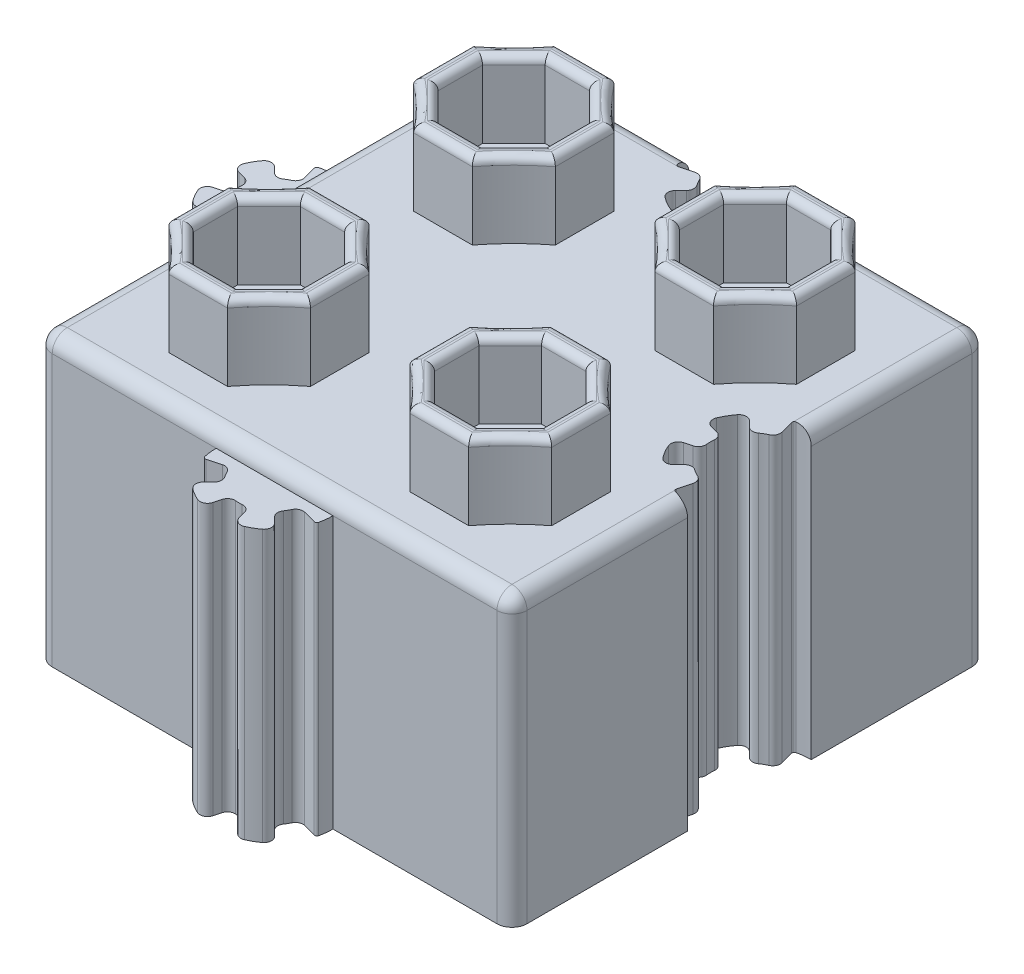
SolidWorks part; units mm, degrees
ref_plane "Front Plane" through (0, 0, 0) normal (0, 0, 1) x (1, 0, 0)
ref_plane "Top Plane" through (0, 0, 0) normal (0, 1, 0) x (1, 0, 0)
ref_plane "Right Plane" through (0, 0, 0) normal (1, 0, 0) x (0, 0, -1)
sketch "Sketch2" plane through (0, 0, 0) normal (0, 1, 0) x (1, 0, 0)
  line L1 (-15.75, 15.75) -> (15.75, 15.75)
  line L2 (-15.75, 15.75) -> (-15.75, -15.75)
  line L3 (-15.75, -15.75) -> (15.75, -15.75)
  line L4 (15.75, 15.75) -> (15.75, -15.75)
  line L5 (-15.75, 15.75) -> (15.75, -15.75) construction
  line L6 (-15.75, -15.75) -> (15.75, 15.75) construction
  point P0 (0, 0)
  dimension "D1" = 31.5
  dimension "D2" = 31.5
extrude "Boss-Extrude1" add sketch "Sketch2" along normal blind 19
sketch "Sketch3" plane through (0, 19, 0) normal (0, 1, 0) x (1, 0, 0)
  line L97 (-15.75, 15.75) -> (-8, 15.75)
  line L98 (15.75, 15.75) -> (-15.75, 15.75) construction
  line L101 (-15.75, 15.75) -> (-15.75, 8)
  line L102 (-15.75, 15.75) -> (-15.75, -15.75) construction
  line L103 (-3.3, 6.1743) -> (-3.3, 10.0679)
  line L105 (-6.0532, 12.8211) -> (-9.9468, 12.8211)
  line L107 (-12.7, 10.0679) -> (-12.7, 6.1743)
  line L109 (-9.9468, 3.4211) -> (-6.0532, 3.4211)
  line L110 (-6.5295, 4.5711) -> (-4.45, 6.6506)
  line L111 (-4.45, 6.6506) -> (-4.45, 9.5916)
  line L112 (-4.45, 9.5916) -> (-6.5295, 11.6711)
  line L113 (-6.5295, 11.6711) -> (-9.4705, 11.6711)
  line L114 (-9.4705, 11.6711) -> (-11.55, 9.5916)
  line L115 (-11.55, 9.5916) -> (-11.55, 6.6506)
  line L116 (-11.55, 6.6506) -> (-9.4705, 4.5711)
  line L117 (-9.4705, 4.5711) -> (-6.5295, 4.5711)
  line L118 (-9.9468, 12.8211) -> (-12.7, 10.0679) [skipped]
  line L119 (-3.3, 10.0679) -> (-6.0532, 12.8211) [skipped]
  line L120 (-6.0532, 3.4211) -> (-3.3, 6.1743) [skipped]
  line L121 (-12.7, 6.1743) -> (-9.9468, 3.4211) [skipped]
  line L125 (9.4705, 4.5711) -> (6.5295, 4.5711)
  line L126 (11.55, 6.6506) -> (9.4705, 4.5711)
  line L127 (11.55, 9.5916) -> (11.55, 6.6506)
  line L128 (9.4705, 11.6711) -> (11.55, 9.5916)
  line L129 (6.5295, 11.6711) -> (9.4705, 11.6711)
  line L130 (4.45, 9.5916) -> (6.5295, 11.6711)
  line L131 (4.45, 6.6506) -> (4.45, 9.5916)
  line L132 (6.5295, 4.5711) -> (4.45, 6.6506)
  line L133 (9.9468, 3.4211) -> (6.0532, 3.4211)
  line L134 (12.7, 10.0679) -> (12.7, 6.1743)
  line L135 (6.0532, 12.8211) -> (9.9468, 12.8211)
  line L136 (3.3, 6.1743) -> (3.3, 10.0679)
  line L137 (3.3, -6.1743) -> (3.3, -10.0679)
  line L138 (6.0532, -12.8211) -> (9.9468, -12.8211)
  line L139 (12.7, -10.0679) -> (12.7, -6.1743)
  line L140 (9.9468, -3.4211) -> (6.0532, -3.4211)
  line L141 (6.5295, -4.5711) -> (4.45, -6.6506)
  line L142 (4.45, -6.6506) -> (4.45, -9.5916)
  line L143 (4.45, -9.5916) -> (6.5295, -11.6711)
  line L144 (6.5295, -11.6711) -> (9.4705, -11.6711)
  line L145 (9.4705, -11.6711) -> (11.55, -9.5916)
  line L146 (11.55, -9.5916) -> (11.55, -6.6506)
  line L147 (11.55, -6.6506) -> (9.4705, -4.5711)
  line L148 (9.4705, -4.5711) -> (6.5295, -4.5711)
  line L149 (-9.4705, -4.5711) -> (-6.5295, -4.5711)
  line L150 (-11.55, -6.6506) -> (-9.4705, -4.5711)
  line L151 (-11.55, -9.5916) -> (-11.55, -6.6506)
  line L152 (-9.4705, -11.6711) -> (-11.55, -9.5916)
  line L153 (-6.5295, -11.6711) -> (-9.4705, -11.6711)
  line L154 (-4.45, -9.5916) -> (-6.5295, -11.6711)
  line L155 (-4.45, -6.6506) -> (-4.45, -9.5916)
  line L156 (-6.5295, -4.5711) -> (-4.45, -6.6506)
  line L157 (-9.9468, -3.4211) -> (-6.0532, -3.4211)
  line L158 (-12.7, -10.0679) -> (-12.7, -6.1743)
  line L159 (-6.0532, -12.8211) -> (-9.9468, -12.8211)
  line L160 (-3.3, -6.1743) -> (-3.3, -10.0679)
  arc A2 (-12.7, 10.0679) -> (-9.9468, 12.8211) centre (-21.8403, 21.9614) ccw
  arc A3 (-6.0532, 12.8211) -> (-3.3, 10.0679) centre (5.8403, 21.9614) ccw
  arc A4 (-6.0532, 3.4211) -> (-3.3, 6.1743) centre (5.8403, -5.7192) cw
  arc A5 (-9.9468, 3.4211) -> (-12.7, 6.1743) centre (-21.8403, -5.7192) ccw
  arc A6 (9.9468, 3.4211) -> (12.7, 6.1743) centre (21.8403, -5.7192) cw
  arc A7 (6.0532, 3.4211) -> (3.3, 6.1743) centre (-5.8403, -5.7192) ccw
  arc A8 (6.0532, 12.8211) -> (3.3, 10.0679) centre (-5.8403, 21.9614) cw
  arc A9 (12.7, 10.0679) -> (9.9468, 12.8211) centre (21.8403, 21.9614) cw
  arc A10 (12.7, -10.0679) -> (9.9468, -12.8211) centre (21.8403, -21.9614) ccw
  arc A11 (6.0532, -12.8211) -> (3.3, -10.0679) centre (-5.8403, -21.9614) ccw
  arc A12 (6.0532, -3.4211) -> (3.3, -6.1743) centre (-5.8403, 5.7192) cw
  arc A13 (9.9468, -3.4211) -> (12.7, -6.1743) centre (21.8403, 5.7192) ccw
  arc A14 (-9.9468, -3.4211) -> (-12.7, -6.1743) centre (-21.8403, 5.7192) cw
  arc A15 (-6.0532, -3.4211) -> (-3.3, -6.1743) centre (5.8403, 5.7192) ccw
  arc A16 (-6.0532, -12.8211) -> (-3.3, -10.0679) centre (5.8403, -21.9614) cw
  arc A17 (-12.7, -10.0679) -> (-9.9468, -12.8211) centre (-21.8403, -21.9614) cw
  point P4 (-8, 8.1211)
  point P52 (8, 8.1211)
  point P95 (8, -8.1211)
  point P96 (-8, -8.1211)
  dimension "D3" = 15
  dimension "D4" = 15
  dimension "D5" = 15
  dimension "D6" = 15
  dimension "D1" = 7.75
  dimension "D2" = 7.75
sketch "Sketch5" plane through (0, 19, 0) normal (0, 1, 0) x (1, 0, 0)
  line L0 (15.75, 15.75) -> (-15.75, 15.75) construction
  line L1 (0.647, 13.3352) -> (1.0353, 11.8863)
  line L2 (-4, 15.75) -> (4, 15.75)
  line L3 (-2.4148, 15.103) -> (-3.8637, 14.7147)
  line L4 (-1.7678, 13.9822) -> (-2.8284, 12.9216)
  line L5 (2.4148, 15.103) -> (3.8637, 14.7147)
  line L6 (-0.647, 13.3352) -> (-1.0353, 11.8863)
  line L7 (1.7678, 13.9822) -> (2.8284, 12.9216)
  line L8 (0, 15.75) -> (4, 15.75)
  line L10 (15.75, 2.6) -> (15.75, -2.6)
  line L12 (15.75, -15.75) -> (15.75, 15.75) construction
  line L16 (13.2386, 0.6729) -> (11.7897, 1.0612)
  line L18 (13.9115, 1.8385) -> (12.8509, 2.8991)
  line L20 (15.0771, 2.5114) -> (14.6888, 3.9603)
  line L21 (15.75, 2.6) -> (15.75, 4.1)
  line L33 (15.75, -2.6) -> (15.75, -4.1)
  line L34 (15.0771, -2.5114) -> (14.6888, -3.9603)
  line L36 (13.9115, -1.8385) -> (12.8509, -2.8991)
  line L38 (13.2386, -0.6729) -> (11.7897, -1.0612)
  arc A0 (-4, 15.75) -> (4, 15.75) centre (0, 15.75) ccw
  arc A1 (-2.4148, 15.103) -> (-1.7678, 13.9822) centre (0, 15.75) ccw
  arc A4 (15.75, 4.1) -> (15.75, -4.1) centre (15.75, 0) ccw
  arc A5 (15.0771, 2.5114) -> (13.9115, 1.8385) centre (15.75, 0) ccw
  arc A6 (13.2386, 0.6729) -> (13.2386, -0.6729) centre (15.75, 0) ccw
  arc A7 (13.9115, -1.8385) -> (15.0771, -2.5114) centre (15.75, 0) ccw
  arc A8 (1.7678, 13.9822) -> (2.4148, 15.103) centre (0, 15.75) ccw
  arc A9 (-0.647, 13.3352) -> (0.647, 13.3352) centre (0, 15.75) ccw
  point P52 (15.75, 0)
  line M12 (15.75, -15.75) -> (15.75, 15.75)
  line M13 (15.75, 15.75) -> (-15.75, 15.75)
  dimension "D1" = 5
  dimension "D4" = 5.2
  dimension "D2" = 4
  dimension "D3" = 8.2
extrude "Cut-Extrude6" cut sketch "Sketch5" against normal through all contours L6 A9 L1 A0 L7 A8 L5 L2 L3 A1 L4 M13 | L36 A7 L34 A4 L20 A5 L18 L16 A6 L38 M12 region at (0, 19, -14.2637) region at (14.2251, 19, 0)
sketch "Sketch6" plane through (0, 19, 0) normal (0, 1, 0) x (1, 0, 0)
  line L0 (-15.75, -15.75) -> (15.75, -15.75) construction
  line L2 (-2.2941, -16.3647) -> (-3.743, -16.7529)
  line L9 (-1.6794, -17.4294) -> (-2.74, -18.49)
  line L10 (-0.6201, -18.0426) -> (-1.0118, -19.4906)
  line L11 (0.6201, -18.0426) -> (1.0118, -19.4906)
  line L12 (1.6794, -17.4294) -> (2.74, -18.49)
  line L13 (2.2941, -16.3647) -> (3.743, -16.7529)
  line L14 (-1, -15.75) -> (1, -15.75)
  line L15 (-2.375, -15.75) -> (2.375, -15.75)
  line L16 (-15.75, 0) -> (-15.75, 2.375)
  line L17 (-15.75, 15.75) -> (-15.75, -15.75) construction
  line L18 (-15.75, 2.375) -> (-15.75, -2.375)
  line L19 (-15.75, 3.875) -> (-15.75, -3.875)
  line L20 (-3.875, -15.75) -> (3.875, -15.75)
  line L21 (-16.3647, 2.2941) -> (-16.7529, 3.743)
  line L22 (-16.3647, -2.2941) -> (-16.7529, -3.743)
  line L23 (-17.4294, 1.6794) -> (-18.49, 2.74)
  line L24 (-18.0441, 0.6147) -> (-19.493, 1.0029)
  line L25 (-17.4294, -1.6794) -> (-18.49, -2.74)
  line L26 (-18.0441, -0.6147) -> (-19.493, -1.0029)
  line L27 (-15.75, 2.375) -> (-15.75, -2.375)
  arc A4 (-3.743, -16.7529) -> (-2.74, -18.49) centre (0, -15.75) ccw
  arc A5 (-1.0118, -19.4906) -> (1.0118, -19.4906) centre (0, -15.75) ccw
  arc A6 (2.74, -18.49) -> (3.743, -16.7529) centre (0, -15.75) ccw
  arc A13 (-0.6201, -18.0426) -> (-0.6147, -18.0441) centre (0, -15.75) ccw
  arc A21 (-16.7529, 3.743) -> (-18.49, 2.74) centre (-15.75, 0) ccw
  arc A23 (-19.493, 1.0029) -> (-19.493, -1.0029) centre (-15.75, 0) ccw
  arc A24 (-18.49, -2.74) -> (-16.7529, -3.743) centre (-15.75, 0) ccw
  arc A25 (-16.3647, 2.2941) -> (-17.4294, 1.6794) centre (-15.75, 0) ccw
  arc A27 (-18.0441, 0.6147) -> (-18.0441, -0.6147) centre (-15.75, 0) ccw
  arc A28 (-15.75, 3.875) -> (-15.75, -3.875) centre (-15.75, 0) ccw
  arc A29 (-3.875, -15.75) -> (3.875, -15.75) centre (0, -15.75) ccw
  arc A30 (-2.2941, -16.3647) -> (-1.6794, -17.4294) centre (0, -15.75) ccw
  arc A31 (-17.4294, -1.6794) -> (-16.3647, -2.2941) centre (-15.75, 0) ccw
  arc A32 (1.6794, -17.4294) -> (2.2941, -16.3647) centre (0, -15.75) ccw
  arc A33 (-0.6201, -18.0426) -> (0.6201, -18.0426) centre (0, -15.75) ccw
  line M21 (-15.75, 15.75) -> (-15.75, -15.75)
  line M22 (-15.75, -15.75) -> (15.75, -15.75)
  dimension "D1" = 7.75
  dimension "D2" = 3.875
  dimension "D5" = 4.75
  dimension "D6" = 7.75
  dimension "D4" = 4.75
  dimension "D7" = 7.75
sketch "Sketch7" plane through (0, 0, 0) normal (0, -1, 0) x (1, 0, 0)
  line L4 (0.6, 14.3) -> (7.5717, 14.3)
  line L6 (-14.325, 14.3) -> (-14.325, 7.3)
  line L7 (14.3, 14.3) -> (14.3, 7.3)
  line L16 (14.3, -14.325) -> (7.3, -14.325)
  line L19 (-14.325, -14.3) -> (-7.325, -14.3)
  line L20 (-14.325, 14.3) -> (-7.325, 14.3)
  line L21 (-0.6038, 14.3) -> (-0.6038, 8.175)
  line L22 (-8.2, 0.6) -> (-4.9639, 0.6)
  line L23 (14.3, -4.26) -> (14.3, -6.725)
  line L24 (-14.325, 14.3) -> (-7.325, 14.3)
  line L25 (-14.325, 0.6) -> (-8.2, 0.6)
  line L26 (-14.325, -0.6) -> (-8.2, -0.6)
  line L27 (-14.325, -0.6) -> (-14.325, -6.725)
  line L29 (0.6, 14.3) -> (0.6, 8.175)
  line L30 (1.0353, 3.8637) -> (0.647, 2.4148)
  line L31 (-8.2, -0.6) -> (-4.9639, -0.6)
  line L33 (2.8284, 2.8284) -> (1.7678, 1.7678)
  line L34 (12.65, -7.025) -> (12.65, -6.725)
  line L36 (-14.325, -5.275) -> (-14.325, -6.725)
  line L39 (-7.325, 14.3) -> (-7.325, 12.65)
  line L40 (-7.325, 12.65) -> (-6.725, 12.65)
  line L41 (-6.725, 12.65) -> (-6.725, 14.3)
  line L47 (-7.325, -14.3) -> (-7.325, -12.65)
  line L48 (-7.325, -12.65) -> (-6.725, -12.65)
  line L49 (-6.725, -12.65) -> (-6.725, -14.3)
  line L50 (-14.325, -7.3) -> (-14.325, -14.3)
  line L51 (8.1717, 12.65) -> (7.5717, 12.65)
  line L52 (7.3, -12.525) -> (7.3, -14.325)
  line L53 (7.5717, 12.65) -> (7.5717, 14.3)
  line L54 (-6.725, -14.3) -> (-4.26, -14.3)
  line L55 (-14.325, 7.3) -> (-12.525, 7.3)
  line L56 (-12.675, -6.7) -> (-12.675, -7.3)
  line L57 (-14.325, 6.7) -> (-12.525, 6.7)
  line L58 (8.1717, 12.65) -> (8.1717, 14.3)
  line L59 (6.7, -14.325) -> (4.2684, -14.325)
  line L60 (7.3, -12.525) -> (6.7, -12.525)
  line L61 (6.7, -12.525) -> (6.7, -14.325)
  line L62 (-12.525, 6.7) -> (-12.525, 7.3)
  line L64 (12.5, 7) -> (12.5, 7.3)
  line L65 (12.5, 7.3) -> (14.3, 7.3)
  line L67 (14.3, 6.7) -> (12.5, 6.7)
  line L68 (12.5, 6.7) -> (12.5, 7)
  line L69 (12.65, -6.725) -> (14.3, -6.725)
  line L71 (-12.675, -6.7) -> (-12.675, -6.725)
  line L72 (-12.675, -6.725) -> (-14.325, -6.725)
  line L73 (-12.675, -7.3) -> (-14.325, -7.3)
  line L74 (14.3, -7.325) -> (12.65, -7.325)
  line L75 (12.65, -7.325) -> (12.65, -7.025)
  line L84 (5.0205, 3.9598) -> (4.0279, 2.9624)
  line L90 (3.8637, 1.0353) -> (2.4148, 0.647)
  line L97 (4.4901, 4.4901) -> (5.0205, 3.9598)
  line L98 (3.8637, -1.0353) -> (2.4148, -0.647)
  line L99 (8.2, 0.6) -> (11.2902, 0.6)
  line L100 (8.2, -0.6) -> (11.2902, -0.6)
  line L101 (-0.6038, -8.175) -> (-0.6038, -11.2907)
  line L102 (0.6, -8.175) -> (0.6, -11.2902)
  line L103 (-4.4901, 4.4901) -> (-3.9598, 5.0205)
  line L104 (2.8284, -2.8284) -> (1.7678, -1.7678)
  line L105 (-3.9598, 5.0205) -> (-2.9652, 4.0259)
  line L106 (1.0353, -3.8637) -> (0.647, -2.4148)
  line L107 (-4.4901, 4.4901) -> (-5.0205, 3.9598)
  line L108 (-1.0353, -3.8637) -> (-0.647, -2.4148)
  line L109 (-5.0205, 3.9598) -> (-4.0279, 2.9624)
  line L110 (-2.8284, -2.8284) -> (-1.7678, -1.7678)
  line L111 (3.9598, 5.0205) -> (2.9652, 4.0259)
  line L112 (-3.8637, -1.0353) -> (-2.4148, -0.647)
  line L113 (-6.725, 14.3) -> (-0.6038, 14.3)
  line L114 (8.1717, 14.3) -> (14.3, 14.3)
  line L115 (14.3, 6.7) -> (14.3, 4.26)
  line L116 (-14.325, 6.7) -> (-14.325, 0.6)
  line L117 (7.3, -14.325) -> (14.3, -14.325)
  line L118 (14.3, -7.325) -> (14.3, -14.325)
  line L119 (4.4901, 4.4901) -> (3.9598, 5.0205)
  line L120 (-3.8637, 1.0353) -> (-2.4148, 0.647)
  line L121 (5.0205, -3.9598) -> (4.0279, -2.9624)
  line L122 (-2.8284, 2.8284) -> (-1.7678, 1.7678)
  line L123 (4.4901, -4.4901) -> (5.0205, -3.9598)
  line L124 (-1.0353, 3.8637) -> (-0.647, 2.4148)
  line L130 (4.4901, -4.4901) -> (3.9598, -5.0205)
  line L131 (3.9598, -5.0205) -> (2.9652, -4.0259)
  line L132 (-5.0205, -3.9598) -> (-4.0279, -2.9624)
  line L133 (-4.4901, -4.4901) -> (-5.0205, -3.9598)
  line L134 (-4.4901, -4.4901) -> (-3.9598, -5.0205)
  line L135 (-3.9598, -5.0205) -> (-2.9652, -4.0259)
  line L136 (8.2, 0.6) -> (4.9639, 0.6)
  line L137 (8.2, -0.6) -> (4.9639, -0.6)
  line L138 (-0.6038, 8.175) -> (-0.6038, 4.9634)
  line L139 (0.6, 8.175) -> (0.6, 4.9639)
  line L140 (-0.6038, -8.175) -> (-0.6038, -4.9634)
  line L141 (0.6, -8.175) -> (0.6, -4.9639)
  line L142 (4.2684, -14.325) -> (6.7, -14.325)
  arc A4 (-4.0279, 2.9624) -> (-4.9639, 0.6) centre (0, 0) ccw
  circle A5 centre (0, 0) radius 4
  arc A6 (0.647, 2.4148) -> (-0.647, 2.4148) centre (0, 0) ccw
  arc A7 (2.4148, 0.647) -> (1.7678, 1.7678) centre (0, 0) ccw
  arc A8 (1.7678, -1.7678) -> (2.4148, -0.647) centre (0, 0) ccw
  arc A9 (-0.647, -2.4148) -> (0.647, -2.4148) centre (0, 0) ccw
  arc A10 (-2.4148, -0.647) -> (-1.7678, -1.7678) centre (0, 0) ccw
  arc A11 (-1.7678, 1.7678) -> (-2.4148, 0.647) centre (0, 0) ccw
  arc A12 (2.9652, 4.0259) -> (0.6, 4.9639) centre (0, 0) ccw
  arc A13 (4.0279, -2.9624) -> (4.9639, -0.6) centre (0, 0) ccw
  arc A14 (-2.9652, -4.0259) -> (-0.6038, -4.9634) centre (0, 0) ccw
  arc A15 (-0.6038, 4.9634) -> (-2.9652, 4.0259) centre (0, 0) ccw
  arc A16 (4.9639, 0.6) -> (4.0279, 2.9624) centre (0, 0) ccw
  arc A17 (-4.9639, -0.6) -> (-4.0279, -2.9624) centre (0, 0) ccw
  arc A18 (0.6, -4.9639) -> (2.9652, -4.0259) centre (0, 0) ccw
  arc A19 (14.3, 4.26) -> (14.3, -4.26) centre (15.75, 0) ccw
  arc A20 (4.2684, -14.325) -> (-4.26, -14.3) centre (0, -15.75) ccw
  point P2 (0, 0)
  point P106 (0, 0)
  dimension "D4" = 10
  dimension "D5" = 8
  dimension "D12" = 5
  dimension "D13" = 9
  dimension "D14" = 9
  dimension "D1" = 1.8
  dimension "D2" = 1.65
  dimension "D3" = 1.65
  dimension "D6" = 0.6
  dimension "D7" = 1.8
  dimension "D8" = 1.65
  dimension "D9" = 1.65
  dimension "D10" = 1.8
  dimension "D11" = 1.65
  dimension "D17" = 7
  dimension "D18" = 0.6
  dimension "D19" = 0.6
  dimension "D20" = 0.3
  dimension "D21" = 0.3
  dimension "D22" = 7
  dimension "D23" = 7
  dimension "D24" = 0.6
  dimension "D25" = 0.3
  dimension "D26" = 0.3
  dimension "D27" = 7
  dimension "D28" = 7
  dimension "D29" = 0.6
  dimension "D30" = 7
  dimension "D31" = 7
  dimension "D32" = 0.75
  dimension "D33" = 0.75
fillet "Fillet20" radius 1 10 edges at (15.75, 9.5, 15.75) (15.75, 9.5, -15.75) (-15.75, 9.5, -15.75) (-15.75, 9.5, 15.75) (-9.875, 19, -15.75) (9.875, 19, -15.75) (15.75, 19, 9.925) (15.75, 19, -9.925) (0, 19, 15.75) (-15.75, 19, 0)
extrude "Boss-Extrude7" add sketch "Sketch6" against normal through all from offset 1 contours L21 A21 L23 L24 A23 L26 L25 A24 L22 M21 | L11 L12 A6 L13 L2 A4 L9 A13 L10 A5 M22 region at (0, 19, 17.1861) region at (-17.1883, 19, 0) offset against normal yes
sketch "Sketch16" plane through (0, 0, 0) normal (0, -1, 0) x (1, 0, 0)
  line L0 (-14.3, 14.3) -> (-8.175, 14.3)
  line L4 (-6.725, 12.6) -> (-6.725, 14.3) construction
  line L5 (-6.725, 14.3) -> (-0.6038, 14.3) construction
  line L9 (8.1717, 14.3) -> (14.3, 14.3)
  line L10 (14.3, 14.3) -> (14.3, 8.175)
  line L11 (14.3, 14.3) -> (14.3, 8.175) construction
  line L12 (14.3, 14.3) -> (14.3, 8.175) construction
  line L16 (14.3, 6.725) -> (14.3, 4.6233)
  line L17 (14.3, -4.6233) -> (14.3, -6.725)
  line L18 (14.3, -6.725) -> (12.6, -6.725)
  line L21 (14.3, -8.175) -> (14.3, -14.3)
  line L22 (14.3, -14.3) -> (8.3504, -14.3)
  line L23 (14.3, -14.3) -> (8.1717, -14.3) construction
  line L24 (8.3504, -14.3) -> (8.1717, -14.3)
  line L28 (6.7217, -14.3) -> (4.6233, -14.3)
  line L29 (-4.6233, -14.3) -> (-6.725, -14.3)
  line L31 (-8.175, -14.3) -> (-14.3, -14.3)
  line L32 (-14.3, -14.3) -> (-14.3, -8.175)
  line L35 (-14.3, -6.725) -> (-14.3, 6.725)
  line L38 (-14.3, 8.175) -> (-14.3, 14.3)
  line L42 (-6.725, 14.3) -> (6.7217, 14.3)
  line L44 (14.3, 8.175) -> (12.6, 8.175)
  line L45 (14.3, 6.725) -> (12.6, 6.725)
  line L46 (12.5, 8.075) -> (12.5, 6.825)
  line L47 (8.1717, 14.3) -> (8.1717, 12.6)
  line L48 (6.7217, 14.3) -> (6.7217, 12.6)
  line L49 (6.8217, 12.5) -> (8.0717, 12.5)
  line L50 (-8.175, 14.3) -> (-8.175, 12.6)
  line L51 (-6.725, 14.3) -> (-6.725, 12.6)
  line L52 (-8.075, 12.5) -> (-6.825, 12.5)
  line L53 (-14.3, 8.175) -> (-12.6, 8.175)
  line L54 (-14.3, 6.725) -> (-12.6, 6.725)
  line L55 (-12.5, 8.075) -> (-12.5, 6.825)
  line L56 (14.3, -8.175) -> (12.6, -8.175)
  line L57 (12.5, -6.825) -> (12.5, -8.075)
  line L58 (8.1717, -14.3) -> (8.1717, -12.6)
  line L59 (-6.725, -12.6) -> (-6.725, -14.3)
  line L60 (8.0717, -12.5) -> (6.8217, -12.5)
  line L61 (8.0717, -12.5) -> (6.8217, -12.5) construction
  line L63 (6.7217, -12.6) -> (6.7217, -14.3)
  line L64 (-14.3, -8.175) -> (-12.6, -8.175)
  line L65 (-6.825, -12.5) -> (-8.075, -12.5)
  line L66 (8.175, -0.6) -> (11.3911, -0.6) construction
  line L67 (-8.175, -12.6) -> (-8.175, -14.3)
  line L68 (-12.5, -8.075) -> (-12.5, -6.825)
  line L70 (-12.6, -6.725) -> (-14.3, -6.725)
  line L71 (8.175, 0.6) -> (11.3911, 0.6) construction
  line L73 (4.6233, -14.3) -> (4.5758, -14.3)
  line L75 (6.7217, -14.3) -> (4.1542, -14.3) construction
  line L76 (-4.6233, -14.3) -> (-4.5758, -14.3)
  line L77 (-6.725, -14.3) -> (-4.1542, -14.3) construction
  arc A6 (14.3, 4.6233) -> (10.828, 0.6) centre (15.5903, 0) ccw
  arc A14 (-0.6038, -10.9881) -> (-4.5758, -14.3) centre (0, -15.75) ccw
  arc A15 (10.828, -0.6) -> (14.3, -4.6233) centre (15.5903, 0) ccw
  arc A19 (4.5758, -14.3) -> (0.6005, -10.9877) centre (0, -15.75) ccw
  arc A22 (10.828, 0.6) -> (10.828, -0.6) centre (14.7827, 0) ccw
  arc A24 (-0.6038, -10.9881) -> (0.6005, -10.9877) centre (-0.0003, -14.9423) cw
  arc A31 (-12.5, 8.075) -> (-12.6, 8.175) centre (-12.6, 8.075) ccw construction
  arc A32 (-12.5, 8.075) -> (-12.6, 8.175) centre (-12.6, 8.075) ccw construction
  arc A33 (-12.6, 8.175) -> (-12.5, 8.075) centre (-12.6, 8.075) cw
  arc A34 (-12.6, 6.725) -> (-12.5, 6.825) centre (-12.6, 6.825) ccw
  arc A35 (-8.175, 12.6) -> (-8.075, 12.5) centre (-8.075, 12.6) ccw
  arc A36 (-6.825, 12.5) -> (-6.725, 12.6) centre (-6.825, 12.6) ccw
  arc A37 (6.7217, 12.6) -> (6.8217, 12.5) centre (6.8217, 12.6) ccw
  arc A38 (8.1717, 12.6) -> (8.0717, 12.5) centre (8.0717, 12.6) cw
  arc A39 (12.5, 8.075) -> (12.6, 8.175) centre (12.6, 8.075) cw
  arc A40 (12.5, 6.825) -> (12.6, 6.725) centre (12.6, 6.825) ccw
  arc A41 (12.5, -6.825) -> (12.6, -6.725) centre (12.6, -6.825) cw
  arc A42 (12.5, -8.075) -> (12.6, -8.175) centre (12.6, -8.075) ccw
  arc A43 (8.1717, -12.6) -> (8.0717, -12.5) centre (8.0717, -12.6) ccw
  arc A44 (6.8217, -12.5) -> (6.7217, -12.6) centre (6.8217, -12.6) ccw
  arc A45 (-6.725, -12.6) -> (-6.825, -12.5) centre (-6.825, -12.6) ccw
  arc A46 (-8.075, -12.5) -> (-8.175, -12.6) centre (-8.075, -12.6) ccw
  arc A47 (-12.6, -6.725) -> (-12.5, -6.825) centre (-12.6, -6.825) cw
  arc A48 (-12.6, -8.175) -> (-12.5, -8.075) centre (-12.6, -8.075) ccw
  dimension "D2" = 9.6
  dimension "D1" = 9.6
  dimension "D3" = 4
  dimension "D4" = 4
extrude "Cut-Extrude13" cut sketch "Sketch16" against normal blind 1.5 and the other way blind 2
extrude "Boss-Extrude11" add sketch "Sketch3" along normal blind 5 contours A5 L109 A4 L103 A3 L105 A2 L107 L117 L116 L115 L114 L113 L112 L111 L110 | L134 A9 L135 A8 L136 A7 L133 A6 L125 L132 L131 L130 L129 L128 L127 L126 | A13 L140 A12 L137 A11 L138 A10 L139 L148 L147 L146 L145 L144 L143 L142 L141 | L158 A17 L159 A16 L160 A15 L157 A14 L149 L156 L155 L154 L153 L152 L151 L150 region at (-4.8603, 19, -4.9814) region at (8, 19, -3.554) region at (4.8603, 19, 4.9814) region at (-8, 19, 3.554)
fillet "Fillet33" radius 0.5 64 edges at (-4.45, 24, -8.1211) (-3.3, 24, -8.1211) (-4.7663, 24, -11.3548) (-5.4898, 24, -10.6313) (-8, 24, -11.6711) (-8, 24, -12.8211) (-11.2337, 24, -11.3548) (-12.7, 24, -8.1211) (-10.5102, 24, -10.6313) (-11.55, 24, -8.1211) (-10.5102, 24, -5.6109) (-11.2337, 24, -4.8874) (-8, 24, -3.4211) (-8, 24, -4.5711) (-5.4898, 24, -5.6109) (-4.7663, 24, -4.8874) (8, 24, -12.8211) (11.2337, 24, -11.3548) (4.7663, 24, -11.3548) (3.3, 24, -8.1211) (4.45, 24, -8.1211) (5.4898, 24, -10.6313) (8, 24, -11.6711) (10.5102, 24, -10.6313) (11.55, 24, -8.1211) (12.7, 24, -8.1211) (5.4898, 24, -5.6109) (8, 24, -4.5711) (10.5102, 24, -5.6109) (4.7663, 24, -4.8874) (11.2337, 24, -4.8874) (8, 24, -3.4211) (-11.55, 24, 8.1211) (-10.5102, 24, 10.6313) (-8, 24, 11.6711) (-5.4898, 24, 10.6313) (-3.3, 24, 8.1211) (-4.45, 24, 8.1211) (-10.5102, 24, 5.6109) (-8, 24, 4.5711) (-5.4898, 24, 5.6109) (-4.7663, 24, 4.8874) (-8, 24, 3.4211) (-11.2337, 24, 4.8874) (-12.7, 24, 8.1211) (-11.2337, 24, 11.3548) (-8, 24, 12.8211) (-4.7663, 24, 11.3548) (5.4898, 24, 10.6313) (8, 24, 11.6711) (10.5102, 24, 10.6313) (11.55, 24, 8.1211) (10.5102, 24, 5.6109) (8, 24, 4.5711) (5.4898, 24, 5.6109) (4.45, 24, 8.1211) (3.3, 24, 8.1211) (4.7663, 24, 4.8874) (8, 24, 3.4211) (11.2337, 24, 4.8874) (12.7, 24, 8.1211) (11.2337, 24, 11.3548) (4.7663, 24, 11.3548) (8, 24, 12.8211)
extrude "Cut-Extrude14" cut sketch "Sketch7" against normal blind 15 contours A19 L115 L67 L68 L64 L65 L7 L114 L58 L51 L53 L4 L29 L139 A12 L111 L119 L97 L84 A16 L136 L99 | A15 L138 L21 L113 L41 L40 L39 L20 L6 L55 L62 L57 L116 L25 L22 A4 L109 L107 L103 L105 | A20 L101 L140 A14 L135 L134 L133 L132 A17 L31 L26 L27 L72 L56 L73 L50 L19 L47 L48 L49 L54 | A20 L59 L61 L60 L52 L16 L118 L74 L75 L34 L69 L23 A19 L100 L137 A13 L121 L123 L130 L131 A18 L141 L102 | L122 A11 L120 A5 L112 A10 L110 L108 A9 L106 L104 A8 L98 L90 A7 L33 L30 A6 L124 region at (-8.1691, 0, -7.6296) region at (7.9109, 0, -7.9156) region at (7.6222, 0, 8.1546) region at (-7.8891, 0, 7.8767) region at (0, 0, 0)
sketch "Sketch18" plane through (-14.3, 0, 0) normal (1, 0, 0) x (0, 0, -1)
  line L0 (-0.6, 0) -> (0.6, 0) construction
  line L1 (0.6, 0) -> (-0.6, 0)
  line L2 (0.6, 0) -> (0.6, 1.5)
  line L3 (0.6, 1.5) -> (-0.6, 1.5)
  line L4 (-0.6, 0) -> (-0.6, 1.5)
extrude "Cut-Extrude15" cut sketch "Sketch18" against normal blind 0.025
sketch "Sketch19" plane through (0, 0, 0) normal (0, -1, 0) x (1, 0, 0)
  line L0 (-0.6038, -11.2907) -> (-0.6038, -10.9881)
  line L1 (-0.6038, -4.9634) -> (-0.6038, -11.2907) construction
  line L2 (0.6, -11.2902) -> (0.6, -10.9876)
  line L4 (11.2902, 0.6) -> (10.828, 0.6)
  line L5 (11.2902, -0.6) -> (10.828, -0.6)
  line L6 (4.9639, -0.6) -> (11.2902, -0.6) construction
  line L7 (10.828, -0.6) -> (11.2902, -0.6) construction
  arc A0 (11.2902, 0.6) -> (11.2902, -0.6) centre (15.2449, 0) ccw
  arc A1 (-0.6038, -11.2907) -> (0.6, -11.2902) centre (-0.0002, -15.2449) cw
  arc A2 (0.6, -10.9876) -> (-0.6038, -10.9881) centre (-0.0003, -14.9423) ccw construction
  arc A3 (-0.6038, -10.9881) -> (0.6, -10.9876) centre (-0.0003, -14.9423) cw
  arc A4 (10.828, -0.6) -> (10.828, 0.6) centre (14.7827, 0) cw
  dimension "D1" = 4
  dimension "D2" = 4
extrude "Cut-Extrude16" cut sketch "Sketch19" against normal blind 1.5
fillet "Fillet34" radius 0.5 24 edges at (3.8637, 8.25, 1.0353) (2.4148, 8.25, 0.647) (1.7678, 8.25, 1.7678) (2.8284, 8.25, 2.8284) (3.8637, 8.25, -1.0353) (2.4148, 8.25, -0.647) (2.8284, 8.25, -2.8284) (1.7678, 8.25, -1.7678) (0.647, 8.25, -2.4148) (1.0353, 8.25, -3.8637) (-0.647, 8.25, -2.4148) (-1.0353, 8.25, -3.8637) (-2.8284, 8.25, -2.8284) (-1.7678, 8.25, -1.7678) (-3.8637, 8.25, -1.0353) (-2.4148, 8.25, -0.647) (-2.8284, 8.25, 2.8284) (-1.0353, 8.25, 3.8637) (1.0353, 8.25, 3.8637) (0.647, 8.25, 2.4148) (-1.7678, 8.25, 1.7678) (-0.647, 8.25, 2.4148) (-3.8637, 8.25, 1.0353) (-2.4148, 8.25, 0.647)
fillet "Fillet35" radius 0.2 24 edges at (-5.0205, 8.25, 3.9598) (-3.9598, 8.25, 5.0205) (3.9598, 8.25, 5.0205) (5.0205, 8.25, 3.9598) (5.0205, 8.25, -3.9598) (3.9598, 8.25, -5.0205) (-3.9598, 8.25, -5.0205) (-5.0205, 8.25, -3.9598) (-12.675, 7.5, -7.3) (-12.675, 7.5, -6.725) (-7.325, 7.5, -12.65) (-6.725, 7.5, -12.65) (7.3, 7.5, -12.525) (6.7, 8.25, -12.525) (12.65, 7.5, -6.725) (12.65, 7.5, -7.325) (12.5, 8.25, 6.7) (12.5, 7.5, 7.3) (8.1717, 7.5, 12.65) (7.5717, 7.5, 12.65) (-7.325, 7.5, 12.65) (-6.725, 7.5, 12.65) (-12.525, 7.5, 7.3) (-12.525, 8.25, 6.7)
fillet "Fillet42" radius 0.5 40 edges at (-2.8284, 9.5, -12.9216) (-1.0353, 9.5, -11.8863) (1.0353, 9.5, -11.8863) (2.8284, 9.5, -12.9216) (2.4148, 9.5, -15.103) (1.7678, 9.5, -13.9822) (0.647, 9.5, -13.3352) (-0.647, 9.5, -13.3352) (-1.7678, 9.5, -13.9822) (-2.4148, 9.5, -15.103) (2.2941, 9, 16.3647) (1.6794, 9, 17.4294) (2.74, 9, 18.49) (-0.6201, 9, 18.0426) (0.6201, 9, 18.0426) (1.0118, 9, 19.4906) (-1.0118, 9, 19.4906) (-2.74, 9, 18.49) (-1.6794, 9, 17.4294) (-2.2941, 9, 16.3647) (-16.3647, 9, 2.2941) (-17.4294, 9, 1.6794) (-18.49, 9, 2.74) (-19.493, 9, 1.0029) (-18.0441, 9, 0.6147) (-17.4294, 9, -1.6794) (-18.0441, 9, -0.6147) (-19.493, 9, -1.0029) (-18.49, 9, -2.74) (-16.3647, 9, -2.2941) (12.8509, 9.5, -2.8991) (15.0771, 9.5, -2.5114) (13.9115, 9.5, -1.8385) (11.7897, 9.5, 1.0612) (11.7897, 9.5, -1.0612) (13.2386, 9.5, -0.6729) (13.2386, 9.5, 0.6729) (12.8509, 9.5, 2.8991) (13.9115, 9.5, 1.8385) (15.0771, 9.5, 2.5114)
fillet "Fillet43" radius 0.15 8 edges at (14.6888, 9.5, -3.9603) (14.6888, 9.5, 3.9603) (3.8637, 9.5, -14.7147) (-3.8637, 9.5, -14.7147) (3.743, 9, 16.7529) (-3.743, 9, 16.7529) (-16.7529, 9, 3.743) (-16.7529, 9, -3.743)
